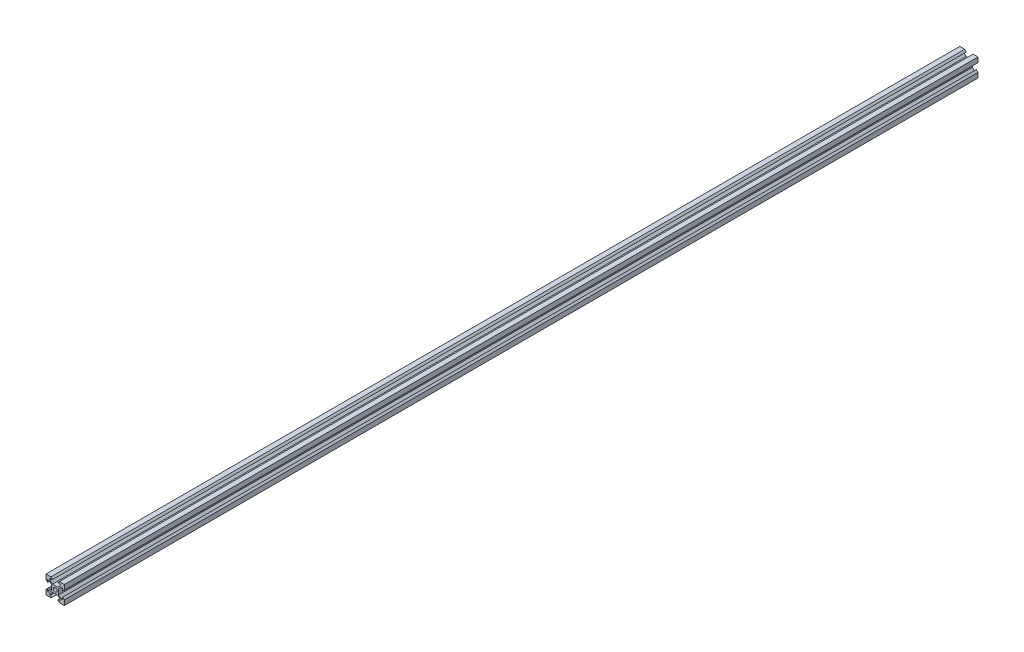
SolidWorks part; units mm, degrees
ref_plane "Front Plane" through (0, 0, 0) normal (0, 0, 1) x (1, 0, 0)
ref_plane "Top Plane" through (0, 0, 0) normal (0, 1, 0) x (1, 0, 0)
ref_plane "Right Plane" through (0, 0, 0) normal (1, 0, 0) x (0, 0, -1)
sketch "Sketch1" plane through (0, 0, 0) normal (0, 0, 1) x (1, 0, 0)
  line L0 (-4.58, 10) -> (-2.885, 8.2)
  line L1 (10, -10) -> (4.58, -10)
  line L2 (10, -10) -> (10, -4.58)
  line L3 (10, 10) -> (4.58, 10)
  line L4 (-10, -10) -> (-10, -4.58)
  line L5 (10, -10) -> (-10, 10) construction
  line L6 (10, 10) -> (-10, -10) construction
  line L7 (-2.8393, 3.9) -> (2.8393, 3.9)
  line L8 (-3.9, 2.8393) -> (-3.9, -2.8393)
  line L9 (-2.8393, -3.9) -> (2.8393, -3.9)
  line L10 (3.9, 2.8393) -> (3.9, -2.8393)
  line L11 (-3.9, 3.9) -> (3.9, -3.9) construction
  line L12 (-3.9, -3.9) -> (3.9, 3.9) construction
  line L13 (4.58, 10) -> (2.885, 8.2)
  line L14 (10, 4.58) -> (10, 10)
  line L15 (-5.5, 8.2) -> (-2.885, 8.2)
  line L16 (-8.2, 5.5) -> (-8.2, 2.885)
  line L17 (-5.5, -8.2) -> (-2.885, -8.2)
  line L18 (8.2, 5.5) -> (8.2, 2.885)
  line L19 (-8.2, 8.2) -> (8.2, -8.2) construction
  line L20 (-8.2, -8.2) -> (8.2, 8.2) construction
  line L21 (10, 4.58) -> (8.2, 2.885)
  line L22 (10, -4.58) -> (8.2, -2.885)
  line L23 (4.58, -10) -> (2.885, -8.2)
  line L24 (-4.58, -10) -> (-2.885, -8.2)
  line L25 (-10, -4.58) -> (-8.2, -2.885)
  line L26 (-10, 4.58) -> (-8.2, 2.885)
  line L27 (0, 14.7958) -> (0, -12.2524) construction
  line L28 (-5.5, 8.2) -> (-5.5, 6.5607)
  line L29 (5.5, 8.2) -> (5.5, 6.5607)
  line L30 (-5.5, 6.5607) -> (-2.8393, 3.9)
  line L31 (2.8393, 3.9) -> (5.5, 6.5607)
  line L32 (-4.58, 10) -> (-10, 10)
  line L33 (2.885, 8.2) -> (5.5, 8.2)
  line L34 (8.2, -2.885) -> (8.2, -5.5)
  line L35 (2.885, -8.2) -> (5.5, -8.2)
  line L36 (-4.58, -10) -> (-10, -10)
  line L37 (-8.2, -2.885) -> (-8.2, -5.5)
  line L38 (-10, 4.58) -> (-10, 10)
  line L39 (8.2, 5.5) -> (6.5607, 5.5)
  line L40 (6.5607, 5.5) -> (3.9, 2.8393)
  line L41 (3.9, -2.8393) -> (6.5607, -5.5)
  line L42 (8.2, -5.5) -> (6.5607, -5.5)
  line L43 (5.5, -8.2) -> (5.5, -6.5607)
  line L44 (5.5, -6.5607) -> (2.8393, -3.9)
  line L45 (-2.8393, -3.9) -> (-5.5, -6.5607)
  line L46 (-5.5, -8.2) -> (-5.5, -6.5607)
  line L47 (-8.2, -5.5) -> (-6.5607, -5.5)
  line L48 (-6.5607, -5.5) -> (-3.9, -2.8393)
  line L49 (-3.9, 2.8393) -> (-6.5607, 5.5)
  line L50 (-8.2, 5.5) -> (-6.5607, 5.5)
  circle A0 centre (0, 0) radius 2.1
  point P0 (0, 0)
  point P35 (0, 0)
  point P41 (-11.9737, 13.3847)
  point P42 (9.3923, -10.2631)
  point P62 (0, 0)
  dimension "D3" = 4.2
  dimension "D1" = 20
  dimension "D4" = 9.16
  dimension "D5" = 9.16
  dimension "D6" = 1.8
  dimension "D7" = 6.1
  dimension "D8" = 5.77
  dimension "D10" = 5.5
  dimension "D11" = 5.5
  dimension "D12" = 1.5
  dimension "D13" = 1.5
  dimension "D14" = 5.77
  dimension "D15" = 20
  dimension "D9" = 4
extrude "Boss-Extrude1" add sketch "Sketch1" along normal blind 1000
